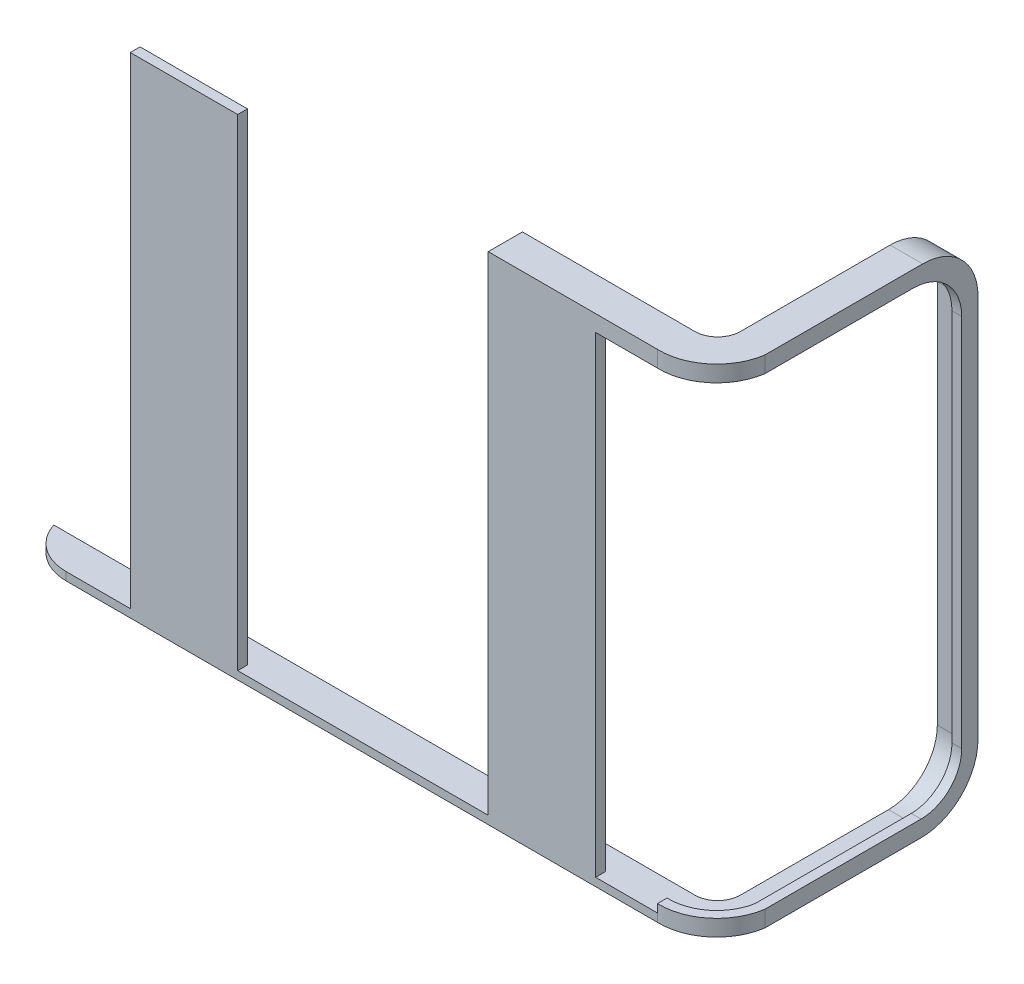
SolidWorks part; units mm, degrees
ref_plane "정면" through (0, 0, 0) normal (0, 0, 1) x (1, 0, 0)
ref_plane "윗면" through (0, 0, 0) normal (0, 1, 0) x (1, 0, 0)
ref_plane "우측면" through (0, 0, 0) normal (1, 0, 0) x (0, 0, -1)
sketch "스케치1" plane through (0, 0, 0) normal (1, 0, 0) x (0, 0, -1)
  line L0 (0, 0) -> (7.5, 0)
  line L1 (7.5, 0) -> (7.5, -2.5)
  line L3 (7.5, -2.5) -> (-3, -2.5)
  line L4 (-3, -2.5) -> (-3, 0)
  line L6 (-3, 0) -> (0, 0)
  dimension "D1" = 3
  dimension "D3" = 7.5
  dimension "D4" = 2.5
extrude "보스-돌출1" add sketch "스케치1" along normal mid plane 211
sketch "스케치5" plane through (105.5, 0, 0) normal (1, 0, 0) x (0, 0, -1)
  line L0 (7.5, 0) -> (60, 0)
  line L1 (7.5, 0) -> (7.5, -2.5)
  line L2 (7.5, -2.5) -> (60, -2.5)
  line L3 (75, 15) -> (77.5, 15) construction
  line L4 (60, 0) -> (60, -2.5) construction
  line L5 (75, 15) -> (75, 148)
  line L6 (75, 148) -> (77.5, 148)
  line L7 (77.5, 148) -> (77.5, 15)
  arc A0 (60, 0) -> (75, 15) centre (60, 15) ccw
  arc A1 (60, -2.5) -> (77.5, 15) centre (60, 15) ccw
  point P14 (74.5675, 148)
  point P15 (0, 0)
  dimension "D1" = 60
  dimension "D2" = 15
  dimension "D3" = 15
  dimension "D4" = 148
extrude "보스-돌출3" add sketch "스케치5" against normal blind 7
fillet "필렛2" radius 15 2 edges at (105.5, -1.25, 3) (-105.5, -1.25, 3)
sketch "스케치6" plane through (0, 0, 0) normal (0, 1, 0) x (1, 0, 0)
  line L0 (90.5, -3) -> (-91.1909, -3) construction
  line L1 (71.5, -3) -> (38.5, -3)
  line L2 (71.5, -3) -> (71.5, 0)
  line L3 (71.5, 0) -> (38.5, 0)
  line L4 (38.5, -3) -> (38.5, 0)
  line L5 (105.5, 60) -> (105.5, 12) construction
  line L10 (0, 0) -> (0, 86.3852) construction
  line L11 (-38.5, -3) -> (-38.5, 0)
  line L12 (-71.5, 0) -> (-38.5, 0)
  line L13 (-71.5, -3) -> (-71.5, 0)
  line L14 (-71.5, -3) -> (-38.5, -3)
  point P8 (0, 86.3852)
  dimension "D1" = 33
  dimension "D2" = 67
  dimension "D3" = 3
extrude "보스-돌출4" add sketch "스케치6" along normal blind 148
sketch "스케치7" plane through (105.5, 0, 0) normal (1, 0, 0) x (0, 0, -1)
  line L0 (75, 148) -> (72.5, 148)
  line L1 (72.5, 148) -> (72.5, 15)
  line L2 (12, 0) -> (12, 2.5)
  line L3 (12, 2.5) -> (60, 2.5)
  line L6 (60, 0) -> (12, 0)
  line L7 (12, 0) -> (12, -2.5)
  line L8 (12, -2.5) -> (60, -2.5)
  line L9 (77.5, 15) -> (77.5, 148)
  line L10 (77.5, 148) -> (75, 148)
  line L11 (75, 148) -> (75, 15)
  line L12 (60, 0) -> (12, 0) construction
  line L13 (12, 0) -> (12, -2.5)
  line L14 (12, -2.5) -> (60, -2.5)
  line L15 (77.5, 15) -> (77.5, 148)
  line L16 (77.5, 148) -> (75, 148)
  line L17 (75, 148) -> (75, 15) construction
  arc A0 (60, 2.5) -> (72.5, 15) centre (60, 15) ccw
  arc A2 (60, -2.5) -> (77.5, 15) centre (60, 15) ccw
  arc A3 (60, 0) -> (75, 15) centre (60, 15) ccw
  arc A4 (60, -2.5) -> (77.5, 15) centre (60, 15) ccw
  arc A5 (60, 0) -> (75, 15) centre (60, 15) ccw construction
  dimension "D2" = 2.5
  dimension "D1" = 0
extrude "보스-돌출5" add sketch "스케치7" along normal blind 3
sketch "스케치8" plane through (0, 0, 0) normal (0, 1, 0) x (1, 0, 0)
  line L0 (105.5, 12) -> (108.5, 12)
  line L1 (90.4936, -0.0387) -> (90.4936, -3)
  arc A1 (90.4936, -0.0387) -> (105.5, 12) centre (91.0546, 14.6343) ccw
  arc A2 (90.5, -3) -> (105.5, 12) centre (90.5, 12) ccw construction
  arc A3 (108.5, 12) -> (90.4936, -3) centre (91.0546, 14.6343) cw
  point P6 (0, 0)
  point P11 (90.5, -3.3526)
  point P12 (105.5, 12)
extrude "보스-돌출6" add sketch "스케치8" along normal mid plane 5
fillet "필렛3" radius 7 1 edges at (98.5, -1.25, -7.5)
sketch "스케치10" plane through (0, 148, 0) normal (0, 1, 0) x (1, 0, 0)
  line L0 (98.5, 77.5) -> (98.5, 14.5)
  line L1 (98.5, 77.5) -> (108.5, 77.5)
  line L2 (108.5, 77.5) -> (108.5, 12)
  line L3 (90.4936, -3) -> (38.5, -3)
  line L4 (38.5, -3) -> (38.5, 7.5)
  line L5 (91.5, 7.5) -> (-105.5, 7.5) construction
  line L6 (38.5, 7.5) -> (91.5, 7.5)
  arc A0 (90.4936, -3) -> (108.5, 12) centre (91.0546, 14.6343) ccw construction
  arc A1 (90.4936, -3) -> (108.5, 12) centre (91.0546, 14.6343) ccw
  arc A2 (91.5, 7.5) -> (98.5, 14.5) centre (91.5, 14.5) ccw construction
  arc A3 (91.5, 7.5) -> (98.5, 14.5) centre (91.5, 14.5) ccw
extrude "보스-돌출7" add sketch "스케치10" along normal blind 2
sketch "스케치11" plane through (0, 148, 0) normal (0, -1, 0) x (1, 0, 0)
  line L0 (105.5, -60) -> (105.5, -75) construction
  line L1 (105.5, -60) -> (105.5, -12) construction
  line L2 (105.5, -60) -> (105.5, -72.5)
  line L3 (105.5, -60) -> (105.5, -12)
  line L5 (108.5, -77.5) -> (108.5, -60) construction
  line L6 (108.5, -12) -> (108.5, -60) construction
  line L7 (108.5, -72.5) -> (108.5, -60)
  line L8 (108.5, -12) -> (108.5, -60)
  line L9 (108.5, -72.5) -> (105.5, -72.5) construction
  line L10 (108.5, -72.5) -> (105.5, -72.5)
  line L11 (90.4936, 0.0387) -> (71.5, 0)
  line L12 (71.5, 0) -> (71.5, 3)
  line L13 (71.5, 3) -> (90.4936, 3)
  arc A0 (105.5, -12) -> (90.4936, 0.0387) centre (91.0546, -14.6343) ccw construction
  arc A1 (105.5, -12) -> (90.4936, 0.0387) centre (91.0546, -14.6343) ccw
  arc A2 (108.5, -12) -> (90.4936, 3) centre (91.0546, -14.6343) ccw construction
  arc A3 (108.5, -12) -> (90.4936, 3) centre (91.0546, -14.6343) ccw
extrude "보스-돌출8" add sketch "스케치11" along normal blind 3
fillet "필렛4" radius 15 2 edges at (107, 145, -72.5) (102, 148, -75)
fillet "필렛5" radius 17 1 edges at (103.5, 150, -77.5)
